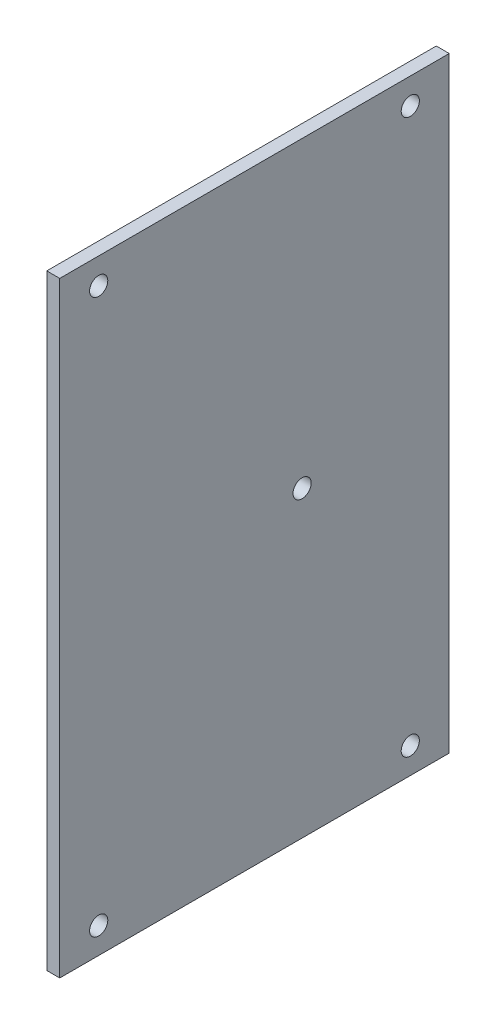
SolidWorks part; units mm, degrees
material "ABS"
ref_plane "Front Plane" through (0, 0, 0) normal (0, 0, 1) x (1, 0, 0)
ref_plane "Top Plane" through (0, 0, 0) normal (0, 1, 0) x (1, 0, 0)
ref_plane "Right Plane" through (0, 0, 0) normal (1, 0, 0) x (0, 0, -1)
sketch "Sketch1" plane through (0, 0, 0) normal (1, 0, 0) x (0, 0, -1)
  line L1 (0, 0) -> (90, 0)
  line L2 (0, 0) -> (0, -140)
  line L3 (0, -140) -> (90, -140)
  line L4 (90, 0) -> (90, -140)
  line L10 (45, 0) -> (45, -70) construction
  circle A0 centre (56, -70) radius 2.1
  circle A8 centre (9, -6) radius 2.1
  circle A9 centre (81, -6) radius 2.1
  circle A10 centre (81, -134) radius 2.1
  circle A11 centre (9, -134) radius 2.1
  point P21 (64.5, -93.5)
  point P26 (49.5, -93.5)
  point P29 (49.5, -85.5)
  dimension "D5" = 4.2
  dimension "D17" = 4.2
  dimension "D3" = 70
  dimension "D14" = 90
  dimension "D2" = 140
  dimension "D15" = 9
  dimension "D16" = 6
  dimension "D4" = 34
extrude "Boss-Extrude1" add sketch "Sketch1" along normal blind 3
equation "\"Depth\"= 90mm"
equation "\"Height\"= 140mm"
equation "\"Width\"= 64mm"
equation "\"D14@Sketch1\"=\"Depth\""
equation "\"D2@Sketch1\"=\"Height\""
